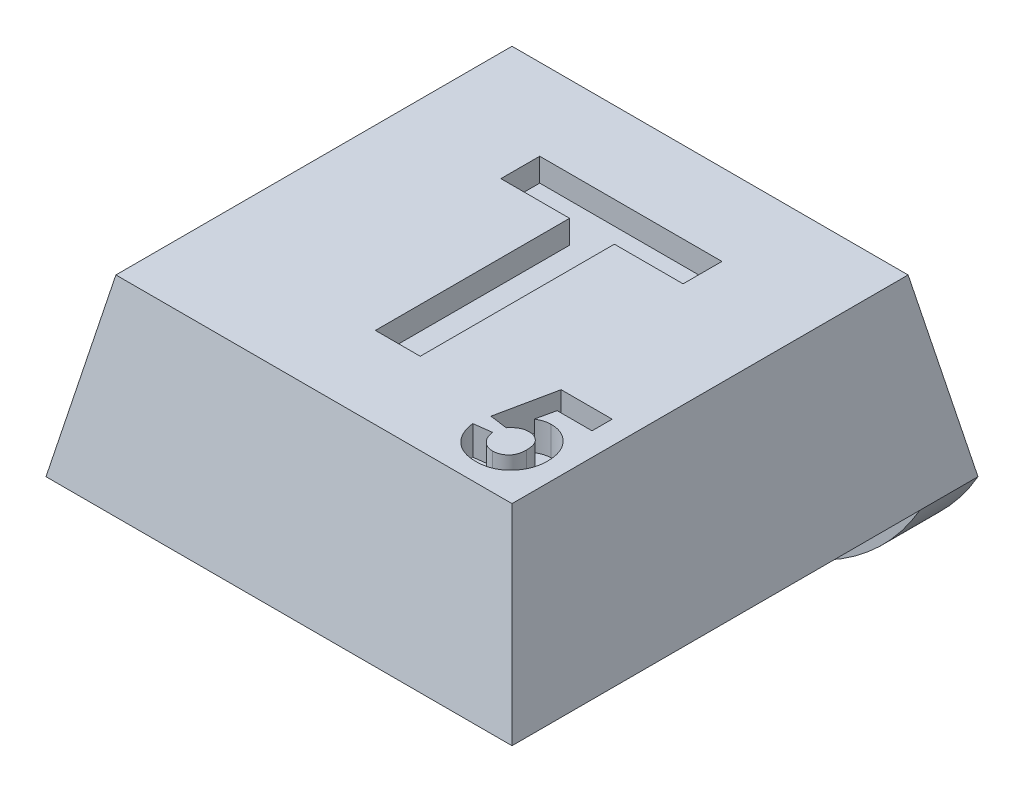
SolidWorks part; units mm, degrees
ref_plane "Front Plane" through (0, 0, 0) normal (0, 0, 1) x (1, 0, 0)
ref_plane "Top Plane" through (0, 0, 0) normal (0, 1, 0) x (1, 0, 0)
ref_plane "Right Plane" through (0, 0, 0) normal (1, 0, 0) x (0, 0, -1)
sketch "Sketch1" plane through (0, 0, 0) normal (0, 1, 0) x (1, 0, 0)
  line L1 (0, 0) -> (8, 0)
  line L2 (0, 0) -> (0, 8)
  line L3 (0, 8) -> (8, 8)
  line L4 (8, 0) -> (8, 8)
  dimension "D1" = 8
  dimension "D2" = 8
extrude "Boss-Extrude1" add sketch "Sketch1" along normal blind 3
sketch "Sketch2" plane through (0, 0, 0) normal (0, 0, 1) x (1, 0, 0)
  line L0 (0, 0) -> (0.6, 3)
  line L1 (0, 3) -> (8, 3) construction
  line L2 (0.6, 3) -> (0, 3)
  line L3 (0, 3) -> (0, 0)
  line L4 (8, 0) -> (7.4, 3)
  line L5 (7.4, 3) -> (8, 3)
  line L6 (8, 3) -> (8, 0)
  dimension "D1" = 0.6
  dimension "D2" = 0.6
extrude "Cut-Extrude1" cut sketch "Sketch2" against normal through all both and the other way through all
sketch "Sketch3" plane through (0, 0, 0) normal (1, 0, 0) x (0, 0, -1)
  line L0 (0, 0) -> (0.6, 3)
  line L1 (8, 3) -> (0, 3) construction
  line L2 (0.6, 3) -> (0, 3)
  line L3 (0, 3) -> (0, 0)
  line L4 (8, 3) -> (7.4, 3)
  line L5 (7.4, 3) -> (8, 0)
  line L6 (8, 3) -> (8, 0)
  dimension "D1" = 0.6
  dimension "D2" = 0.6
extrude "Cut-Extrude2" cut sketch "Sketch3" along normal blind 11
sketch "Sketch4" plane through (0, 0, 0) normal (0, -1, 0) x (1, 0, 0)
  line L0 (8, 0) -> (8, -8) construction
  line L3 (0, 0) -> (8, 0) construction
  circle A0 centre (4, -3.75) radius 1.75
  dimension "D1" = 3.5
  dimension "D2" = 4
  dimension "D3" = 3.75
extrude "Cut-Extrude3" cut sketch "Sketch4" against normal blind 0.4
sketch "Sketch5" plane through (0, 0, 0) normal (0, -1, 0) x (1, 0, 0)
  line L0 (8, 0) -> (8, -8) construction
  line L1 (0, -8) -> (8, -8)
  line L2 (0, -8) -> (0, -7)
  line L3 (0, -7) -> (8, -7)
  line L4 (8, -8) -> (8, -7)
  dimension "D1" = 1
extrude "Boss-Extrude2" add sketch "Sketch5" along normal blind 2
fillet "Fillet1" radius 4 2 edges at (8, -2, -7.5) (0, -2, -7.5)
sketch "Sketch6" plane through (0, 3, 0) normal (0, 1, 0) x (1, 0, 0)
  text T0 "T" font "Arial" height 4
extrude "Cut-Extrude4" cut sketch "Sketch6" against normal blind 0.4
sketch "Sketch7" plane through (0, 3, 0) normal (0, 1, 0) x (1, 0, 0)
  text T0 "5" font "Arial" height 1.8
extrude "Cut-Extrude5" cut sketch "Sketch7" against normal blind 0.5
